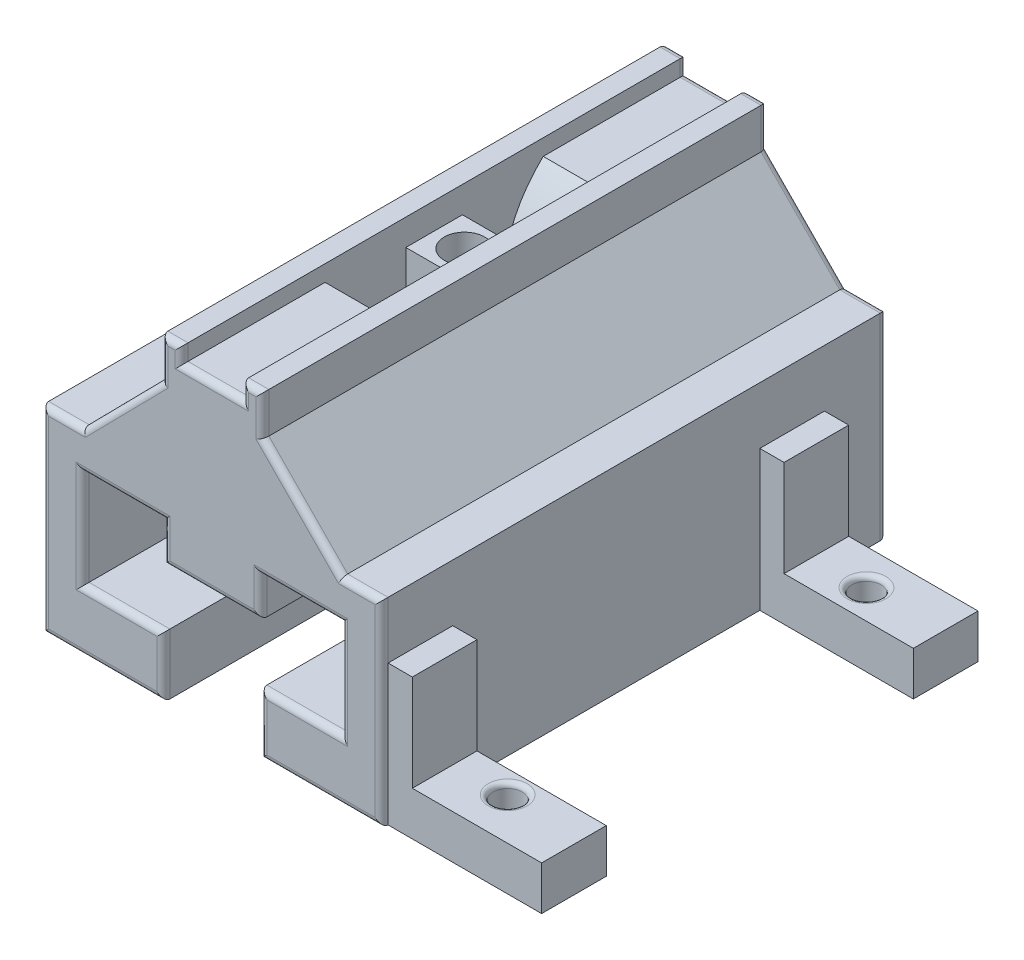
SolidWorks part; units mm, degrees
ref_plane "Front" through (0, 0, 0) normal (0, 0, 1) x (1, 0, 0)
ref_plane "Top" through (0, 0, 0) normal (0, 1, 0) x (1, 0, 0)
ref_plane "Right" through (0, 0, 0) normal (1, 0, 0) x (0, 0, -1)
sketch "Sketch2" plane through (0, 0, 0) normal (0, 0, 1) x (1, 0, 0)
  line L0 (-3.81, 2.6476) -> (-10.16, 2.6476)
  line L1 (-10.16, 2.6476) -> (-10.16, 10.3311)
  line L2 (-10.16, 10.3311) -> (-3.81, 10.3311)
  line L3 (-3.81, 10.3311) -> (-3.81, 7.2831)
  line L4 (-3.81, 7.2831) -> (3.81, 7.2831)
  line L5 (0, -55) -> (0, 55) construction
  line L6 (-3.81, 2.6476) -> (-3.81, -2.1149)
  line L7 (-3.81, -2.1149) -> (-13.335, -2.1149)
  line L8 (-13.335, -2.1149) -> (-13.335, 13.3791)
  line L9 (-13.335, 13.3791) -> (-10.16, 13.3791)
  line L10 (-10.16, 13.3791) -> (-3.9688, 19.6656)
  line L11 (-3.9688, 19.6656) -> (-3.9688, 22.8406)
  line L12 (-3.9688, 22.8406) -> (-2.3813, 22.8406)
  line L13 (-2.3813, 22.8406) -> (-2.3813, 21.5706)
  line L14 (-2.3813, 21.5706) -> (2.3813, 21.5706)
  line L15 (2.3813, 22.8406) -> (2.3813, 21.5706)
  line L16 (3.9688, 22.8406) -> (2.3813, 22.8406)
  line L17 (3.9688, 19.6656) -> (3.9688, 22.8406)
  line L18 (10.16, 13.3791) -> (3.9688, 19.6656)
  line L19 (13.335, 13.3791) -> (10.16, 13.3791)
  line L20 (13.335, -2.1149) -> (13.335, 13.3791)
  line L21 (3.81, -2.1149) -> (13.335, -2.1149)
  line L22 (3.81, 2.6476) -> (3.81, -2.1149)
  line L23 (3.81, 10.3311) -> (3.81, 7.2831)
  line L24 (10.16, 10.3311) -> (3.81, 10.3311)
  line L25 (10.16, 2.6476) -> (10.16, 10.3311)
  line L26 (3.81, 2.6476) -> (10.16, 2.6476)
  point P23 (0, 21.5706)
  point P32 (0, 7.2831)
  dimension "D1" = 4.7625
  dimension "D2" = 9.525
  dimension "D3" = 3.175
  dimension "D4" = 15.494
  dimension "D5" = 3.048
  dimension "D6" = 3.048
  dimension "D7" = 14.2875
  dimension "D8" = 3.175
  dimension "D9" = 1.27
  dimension "D10" = 1.5875
  dimension "D11" = 2.3813
  dimension "D12" = 3.175
  dimension "D13" = 6.35
  dimension "D14" = 3.81
extrude "Boss-Extrude1" add sketch "Sketch2" along normal blind 39.6875
sketch "Sketch3" plane through (0, 21.5706, 0) normal (0, 1, 0) x (1, 0, 0)
  line L0 (0, 0) -> (0, -39.6875) construction
  line L1 (-13.335, -19.8438) -> (13.335, -19.8438) construction
  line L2 (-13.335, -39.6875) -> (-13.335, 0) construction
  line L3 (13.335, -39.6875) -> (13.335, 0) construction
  line L4 (2.3813, 0) -> (-2.3813, 0)
  line L5 (-2.3813, 0) -> (-2.3813, -39.6875)
  line L6 (-2.3813, -39.6875) -> (2.3813, -39.6875)
  line L7 (2.3813, -39.6875) -> (2.3813, 0)
  line L8 (2.3813, 0) -> (-2.3813, 0)
  line L9 (-2.3813, 0) -> (-2.3813, -39.6875)
  line L10 (-2.3813, -39.6875) -> (2.3813, -39.6875)
  line L11 (2.3813, -39.6875) -> (2.3813, 0)
  circle A0 centre (0, -19.8437) radius 1.5875
  dimension "D2" = 3.175
  dimension "D1" = 0
extrude "Cut-Extrude1" cut sketch "Sketch3" against normal blind 39.6875 contours A0 region at (0, 21.5706, 19.8437)
sketch "Sketch4" plane through (0, 7.2831, 0) normal (0, -1, 0) x (1, 0, 0)
  line L1 (0.9165, 18.2562) -> (1.8331, 19.8437)
  line L2 (1.8331, 19.8437) -> (0.9165, 21.4312)
  line L3 (0.9165, 21.4312) -> (-0.9165, 21.4312)
  line L4 (-3.81, 0) -> (3.81, 0)
  line L5 (3.81, 0) -> (3.81, 39.6875)
  line L6 (3.81, 39.6875) -> (-3.81, 39.6875)
  line L7 (-3.81, 39.6875) -> (-3.81, 0)
  line L8 (-3.81, 0) -> (3.81, 0)
  line L9 (3.81, 0) -> (3.81, 39.6875)
  line L10 (3.81, 39.6875) -> (-3.81, 39.6875)
  line L11 (-3.81, 39.6875) -> (-3.81, 0)
  line L12 (-0.9165, 21.4312) -> (-1.8331, 19.8437)
  line L13 (-1.8331, 19.8437) -> (-0.9165, 18.2562)
  line L14 (-0.9165, 18.2562) -> (0.9165, 18.2562)
  circle A0 centre (0, 19.8437) radius 1.5875 construction
  circle M11 centre (0, 19.8437) radius 1.5875
  dimension "D2" = 3.175
  dimension "D1" = 0
extrude "Cut-Extrude3" cut sketch "Sketch4" against normal blind 5 contours M11 | L12 L13 M11 | L13 L14 M11 | L14 L1 M11 | L1 L2 M11 | L2 L3 M11 | L3 L12 M11 region at (0.8204, 7.2831, 18.4228) region at (1.6408, 7.2831, 19.8437) region at (0, 7.2831, 19.8437) region at (-0.8204, 7.2831, 18.4228) region at (-1.6408, 7.2831, 19.8437) region at (0.8204, 7.2831, 21.2647) region at (-0.8204, 7.2831, 21.2647)
sketch "Sketch5" plane through (2.3812, 0, 0) normal (-1, 0, 0) x (0, 0, 1)
  line L3 (11.2713, 21.5706) -> (17.6212, 21.5706)
  line L6 (28.4163, 21.5706) -> (22.0663, 21.5706)
  line L7 (28.1707, 7.2831) -> (20.7963, 7.2831)
  line L8 (22.0663, 10.3311) -> (17.6212, 10.3311)
  line L9 (19.8438, 21.5706) -> (19.8438, 7.2831) construction
  line L12 (11.5168, 7.2831) -> (17.6213, 7.2831)
  line L16 (20.7963, 7.2831) -> (17.6213, 7.2831)
  line L19 (22.0663, 20.7705) -> (17.6212, 20.7705)
  line L21 (17.6212, 20.7705) -> (17.6212, 10.3311)
  line L22 (22.0663, 20.7705) -> (22.0663, 10.3311)
  line L24 (17.6212, 21.5706) -> (22.0663, 21.5706)
  arc A0 (28.4163, 21.5706) -> (28.1707, 7.2831) centre (35.1321, 14.3093) ccw
  arc A1 (11.2713, 21.5706) -> (11.5168, 7.2831) centre (4.5554, 14.3093) cw
  dimension "D1" = 4.445
extrude "Cut-Extrude5" cut sketch "Sketch5" along normal up to surface (4.7625 mm away) up to face at (-2.3813, 22.2056, 19.8438)
sketch "Sketch6" plane through (-2.3812, 0, 0) normal (1, 0, 0) x (0, 0, -1)
  line L0 (-26.0766, 10.3311) -> (-13.6109, 10.3311)
  line L1 (-11.5168, 7.2831) -> (-28.1707, 7.2831)
  line L6 (0, 21.5706) -> (0, 22.8406)
  line L7 (0, 22.8406) -> (-39.6875, 22.8406)
  line L8 (-39.6875, 22.8406) -> (-39.6875, 21.5706)
  line L9 (-39.6875, 21.5706) -> (-28.4163, 21.5706)
  line L10 (-28.1707, 7.2831) -> (-11.5168, 7.2831)
  line L11 (-11.2713, 21.5706) -> (0, 21.5706)
  arc A2 (-28.1707, 7.2831) -> (-28.4163, 21.5706) centre (-35.1321, 14.3093) ccw
  arc A3 (-11.2713, 21.5706) -> (-11.5168, 7.2831) centre (-4.5554, 14.3093) ccw
  arc A4 (-28.1707, 7.2831) -> (-26.0766, 10.3311) centre (-35.1321, 14.3093) ccw
  arc A5 (-13.6109, 10.3311) -> (-11.5168, 7.2831) centre (-4.5554, 14.3093) ccw
  dimension "D1" = 0
extrude "Cut-Extrude6" cut sketch "Sketch6" against normal blind 3.175 and the other way blind 8.255 contours L1 A4 L0 A5
fillet "Fillet1" radius 0.508 52 edges at (-6.985, 2.6476, 0) (-10.16, 6.4894, 0) (-6.985, 10.3311, 0) (-3.81, 8.8071, 0) (0, 7.2831, 0) (3.81, 8.8071, 0) (6.985, 10.3311, 0) (10.16, 6.4894, 0) (6.985, 2.6476, 0) (3.81, 0.2664, 0) (8.5725, -2.1149, 0) (13.335, 5.6321, 0) (11.7475, 13.3791, 0) (7.0644, 16.5224, 0) (3.9688, 21.2531, 0) (3.175, 22.8406, 0) (2.3813, 22.2056, 0) (0, 21.5706, 0) (-2.3813, 22.2056, 0) (-3.175, 22.8406, 0) (-3.9688, 21.2531, 0) (-7.0644, 16.5224, 0) (-11.7475, 13.3791, 0) (-13.335, 5.6321, 0) (-8.5725, -2.1149, 0) (-3.81, 0.2664, 0) (-8.5725, -2.1149, 39.6875) (-13.335, 5.6321, 39.6875) (-11.7475, 13.3791, 39.6875) (-7.0644, 16.5224, 39.6875) (-3.9688, 21.2531, 39.6875) (-3.175, 22.8406, 39.6875) (-2.3813, 22.2056, 39.6875) (0, 21.5706, 39.6875) (2.3813, 22.2056, 39.6875) (3.175, 22.8406, 39.6875) (3.9688, 21.2531, 39.6875) (7.0644, 16.5224, 39.6875) (11.7475, 13.3791, 39.6875) (13.335, 5.6321, 39.6875) (8.5725, -2.1149, 39.6875) (3.81, 0.2664, 39.6875) (6.985, 2.6476, 39.6875) (10.16, 6.4894, 39.6875) (6.985, 10.3311, 39.6875) (3.81, 8.8071, 39.6875) (0, 7.2831, 39.6875) (-3.81, 8.8071, 39.6875) (-6.985, 10.3311, 39.6875) (-10.16, 6.4894, 39.6875) (-6.985, 2.6476, 39.6875) (-3.81, 0.2664, 39.6875)
sketch "Sketch7" plane through (13.335, 0, 0) normal (1, 0, 0) x (0, 0, -1)
  line L0 (-39.1795, -2.1149) -> (-0.508, -2.1149) construction
  line L1 (-39.1795, -2.1149) -> (-34.0995, -2.1149)
  line L2 (-39.1795, -2.1149) -> (-39.1795, 8.9054)
  line L3 (-39.1795, 8.9054) -> (-34.0995, 8.9054)
  line L4 (-34.0995, -2.1149) -> (-34.0995, 8.9054)
  line L5 (-9.9695, -2.1149) -> (-4.8895, -2.1149)
  line L6 (-9.9695, -2.1149) -> (-9.9695, 8.9054)
  line L7 (-9.9695, 8.9054) -> (-4.8895, 8.9054)
  line L8 (-4.8895, -2.1149) -> (-4.8895, 8.9054)
  dimension "D1" = 5.08
  dimension "D2" = 24.13
extrude "Boss-Extrude2" add sketch "Sketch7" along normal blind 1.905
sketch "Sketch8" plane through (15.24, 0, 0) normal (1, 0, 0) x (0, 0, -1)
  line L0 (-39.1795, 1.336) -> (-34.0995, 1.336)
  line L1 (-9.9695, 1.336) -> (-4.8895, 1.336)
  line L4 (-39.1795, 8.9054) -> (-39.1795, -2.1149)
  line L5 (-39.1795, -2.1149) -> (-34.0995, -2.1149)
  line L6 (-34.0995, -2.1149) -> (-34.0995, 8.9054)
  line L7 (-34.0995, 8.9054) -> (-39.1795, 8.9054)
  line L8 (-39.1795, 8.9054) -> (-39.1795, -2.1149)
  line L9 (-39.1795, -2.1149) -> (-34.0995, -2.1149)
  line L10 (-34.0995, -2.1149) -> (-34.0995, 8.9054)
  line L11 (-34.0995, 8.9054) -> (-39.1795, 8.9054)
  line L12 (-9.9695, 8.9054) -> (-9.9695, -2.1149)
  line L13 (-9.9695, -2.1149) -> (-4.8895, -2.1149)
  line L14 (-4.8895, -2.1149) -> (-4.8895, 8.9054)
  line L15 (-4.8895, 8.9054) -> (-9.9695, 8.9054)
  line L16 (-9.9695, 8.9054) -> (-9.9695, -2.1149)
  line L17 (-9.9695, -2.1149) -> (-4.8895, -2.1149)
  line L18 (-4.8895, -2.1149) -> (-4.8895, 8.9054)
  line L19 (-4.8895, 8.9054) -> (-9.9695, 8.9054)
  line M9 (-39.1795, 8.9054) -> (-39.1795, -2.1149)
  line M10 (-39.1795, -2.1149) -> (-34.0995, -2.1149)
  line M11 (-34.0995, -2.1149) -> (-34.0995, 8.9054)
  dimension "D1" = 0
  dimension "D2" = 0
extrude "Boss-Extrude3" add sketch "Sketch8" along normal blind 10.16 contours L0 M9 M10 M11 | L17 L18 L1 L16 region at (15.24, -0.3894, 36.6395) region at (15.24, -0.3894, 7.4295)
sketch "Sketch9" plane through (0, -2.1149, 0) normal (0, -1, 0) x (1, 0, 0)
  line L11 (3.81, 39.1795) -> (3.81, 0.508)
  line L12 (3.81, 0.508) -> (13.335, 0.508)
  line L13 (13.335, 0.508) -> (13.335, 4.8895)
  line L14 (13.335, 4.8895) -> (25.4, 4.8895)
  line L15 (25.4, 4.8895) -> (25.4, 9.9695)
  line L16 (25.4, 9.9695) -> (13.335, 9.9695)
  line L17 (13.335, 9.9695) -> (13.335, 34.0995)
  line L18 (13.335, 34.0995) -> (25.4, 34.0995)
  line L19 (25.4, 34.0995) -> (25.4, 39.1795)
  line L20 (25.4, 39.1795) -> (13.335, 39.1795)
  line L21 (13.335, 39.1795) -> (3.81, 39.1795)
  line L22 (3.81, 39.1795) -> (3.81, 0.508)
  line L23 (3.81, 0.508) -> (13.335, 0.508)
  line L24 (13.335, 0.508) -> (13.335, 4.8895)
  line L25 (13.335, 4.8895) -> (25.4, 4.8895)
  line L26 (25.4, 4.8895) -> (25.4, 9.9695)
  line L27 (25.4, 9.9695) -> (13.335, 9.9695)
  line L28 (13.335, 9.9695) -> (13.335, 34.0995)
  line L29 (13.335, 34.0995) -> (25.4, 34.0995)
  line L30 (25.4, 34.0995) -> (25.4, 39.1795)
  line L31 (25.4, 39.1795) -> (13.335, 39.1795)
  line L32 (13.335, 39.1795) -> (3.81, 39.1795)
  circle A0 centre (19.431, 7.6835) radius 1.143
  circle A1 centre (19.431, 35.8775) radius 1.143
  dimension "D2" = 2.286
  dimension "D4" = 2.286
  dimension "D6" = 6.096
  dimension "D7" = 6.096
  dimension "D3" = 2.286
  dimension "D5" = 1.778
  dimension "D1" = 0
extrude "Cut-Extrude7" cut sketch "Sketch9" against normal up to next contours A1 | A0 region at (19.431, -2.1149, 7.6835) region at (19.431, -2.1149, 35.8775)
fillet "Fillet2" radius 0.381 4 edges at (20.574, -2.1149, 7.6835) (20.574, -2.1149, 35.8775) (18.288, 1.336, 7.6835) (18.288, 1.336, 35.8775)
